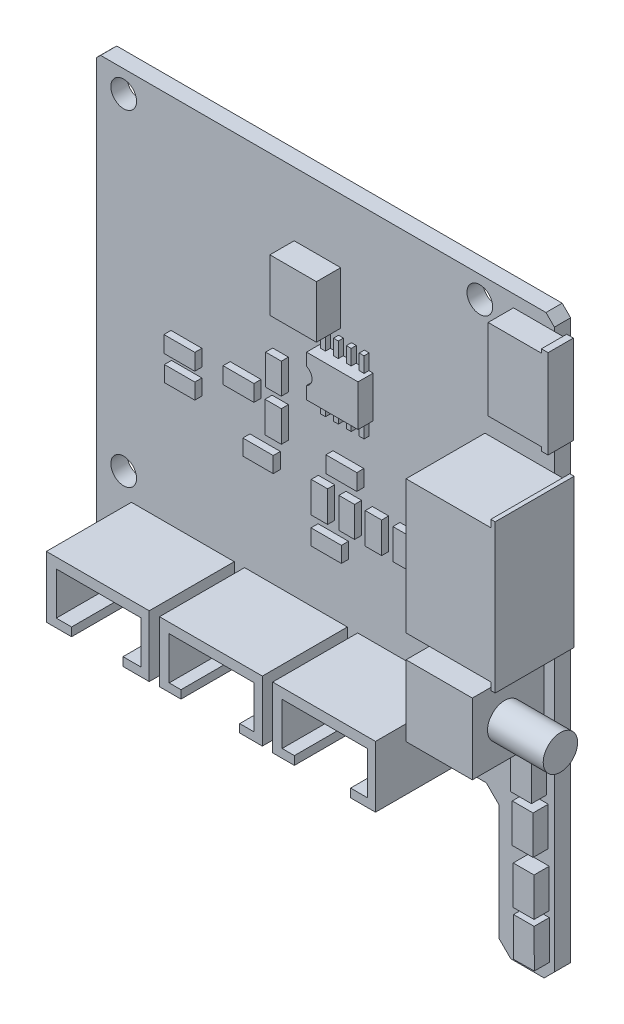
SolidWorks part; units mm, degrees
ref_plane "前视基准面" through (0, 0, 0) normal (0, 0, 1) x (1, 0, 0)
ref_plane "上视基准面" through (0, 0, 0) normal (0, 1, 0) x (1, 0, 0)
ref_plane "右视基准面" through (0, 0, 0) normal (1, 0, 0) x (0, 0, -1)
sketch "Model" plane through (0, 0, 0) normal (0, 0, 1) x (1, 0, 0)
  line L0 (45.593, 67.31) -> (54.991, 57.912)
  line L1 (54.991, 57.912) -> (54.991, 51.054)
  line L2 (54.991, 51.054) -> (56.896, 49.149)
  line L3 (56.896, 49.149) -> (58.801, 49.149)
  line L4 (46.863, 67.31) -> (58.928, 55.245)
  line L5 (58.928, 55.245) -> (58.928, 50.292)
  line L6 (58.928, 50.292) -> (62.992, 46.228)
  line L7 (62.992, 46.228) -> (62.992, 41.529)
  line L8 (62.992, 41.529) -> (65.151, 39.37)
  line L9 (48.133, 67.31) -> (61.214, 54.229)
  line L10 (61.214, 54.229) -> (62.611, 54.229)
  line L11 (62.611, 54.229) -> (65.659, 51.181)
  line L12 (65.659, 51.181) -> (65.659, 47.371)
  line L13 (65.659, 47.371) -> (65.405, 47.117)
  line L14 (65.405, 47.117) -> (65.024, 47.117)
  line L15 (65.024, 47.117) -> (64.897, 46.99)
  line L16 (64.897, 46.99) -> (65.786, 46.101)
  line L17 (65.786, 46.101) -> (65.786, 41.656)
  line L18 (65.151, 37.211) -> (65.786, 37.846)
  line L19 (65.786, 37.846) -> (65.786, 41.656)
  line L20 (65.786, 41.656) -> (65.024, 42.418)
  line L21 (66.167, 32.766) -> (65.151, 32.766)
  line L22 (49.022, 76.327) -> (51.689, 76.327)
  line L23 (44.45, 76.2) -> (46.355, 76.2)
  line L24 (39.624, 64.262) -> (45.339, 64.262)
  line L25 (41.91, 65.659) -> (43.561, 65.659)
  line L26 (43.561, 65.659) -> (44.323, 66.421)
  line L27 (44.323, 66.421) -> (44.323, 66.929)
  line L28 (66.675, 86.5429) -> (66.675, 86.36)
  line L29 (66.675, 86.36) -> (66.675, 86.5427)
  line L30 (66.675, 86.5427) -> (66.675, 31.496)
  line L31 (21.463, 87.0077) -> (21.844, 87.376)
  line L32 (21.844, 87.376) -> (65.8419, 87.376)
  line L33 (65.8419, 87.376) -> (66.675, 86.5429)
  line L34 (21.463, 86.995) -> (21.463, 87.0077)
  line L35 (21.463, 87.0077) -> (21.463, 45.847)
  line L36 (21.463, 45.847) -> (23.114, 44.196)
  line L37 (23.114, 44.196) -> (59.944, 44.196)
  line L38 (59.944, 44.196) -> (61.214, 42.926)
  line L39 (61.214, 42.926) -> (61.214, 31.496)
  line L40 (61.214, 31.496) -> (62.357, 30.353)
  line L41 (62.357, 30.353) -> (65.659, 30.353)
  line L42 (65.659, 30.353) -> (66.675, 31.369)
  line L43 (66.675, 31.369) -> (66.675, 31.496)
  line L44 (57.769, 56.007) -> (58.928, 56.007)
  line L45 (58.928, 56.007) -> (63.119, 51.816)
  line L46 (29.353, 66.548) -> (29.353, 64.008)
  line L47 (28.448, 58.166) -> (29.353, 59.071)
  line L48 (29.353, 59.071) -> (29.353, 64.008)
  line L49 (31.353, 64.008) -> (33.766, 61.595)
  line L50 (33.766, 61.595) -> (37.1, 61.595)
  line L51 (55.769, 56.007) -> (53.848, 57.928)
  line L52 (53.848, 57.928) -> (53.848, 61.468)
  line L53 (53.848, 61.468) -> (54.864, 62.484)
  line L54 (54.864, 62.484) -> (56.007, 62.484)
  line L55 (56.007, 62.484) -> (56.769, 63.246)
  line L56 (56.769, 63.246) -> (56.769, 71.628)
  line L57 (56.769, 71.628) -> (55.753, 72.644)
  line L58 (55.753, 72.644) -> (54.102, 72.644)
  line L59 (54.102, 72.644) -> (53.34, 73.406)
  line L60 (53.34, 73.406) -> (53.34, 74.676)
  line L61 (53.34, 74.676) -> (51.689, 76.327)
  line L62 (64.897, 47.0814) -> (66.04, 45.9384)
  line L63 (66.04, 45.9384) -> (66.04, 42.672)
  line L64 (66.04, 42.672) -> (65.753, 42.3824)
  line L65 (65.753, 42.3824) -> (65.024, 42.3824)
  line L66 (58.801, 49.149) -> (58.8353, 49.1833)
  line L67 (58.8353, 49.1833) -> (64.897, 49.1833)
  line L68 (65.151, 39.4043) -> (63.754, 38.0073)
  line L69 (63.754, 38.0073) -> (63.754, 35.306)
  line L70 (63.754, 35.306) -> (64.2278, 34.8323)
  line L71 (64.2278, 34.8323) -> (65.151, 34.8323)
  line L72 (64.897, 49.1833) -> (63.5, 47.7863)
  line L73 (63.5, 47.7863) -> (63.5, 44.958)
  line L74 (63.5, 44.958) -> (63.9738, 44.4843)
  line L75 (63.9738, 44.4843) -> (65.024, 44.4843)
  line L76 (65.151, 32.7317) -> (66.421, 34.0017)
  line L77 (66.421, 34.0017) -> (66.421, 36.703)
  line L78 (66.421, 36.703) -> (65.8202, 37.3037)
  line L79 (65.8202, 37.3037) -> (65.151, 37.3037)
  line L80 (48.133, 68.7197) -> (48.133, 67.31)
  line L81 (46.863, 68.7197) -> (46.863, 67.31)
  line L82 (45.593, 68.7197) -> (45.593, 67.31)
  line L83 (41.529, 58.293) -> (41.529, 61.325)
  line L84 (41.529, 61.325) -> (43.053, 62.849)
  line L85 (39.1, 61.595) -> (40.132, 60.563)
  line L86 (40.132, 60.563) -> (40.132, 57.531)
  line L87 (40.132, 57.531) -> (40.767, 56.896)
  line L88 (40.767, 56.896) -> (43.45, 56.896)
  line L89 (43.45, 56.896) -> (43.831, 57.277)
  line L90 (48.133, 74.5363) -> (48.133, 75.819)
  line L91 (48.133, 75.819) -> (48.641, 76.327)
  line L92 (48.641, 76.327) -> (49.022, 76.327)
  line L93 (46.355, 76.2) -> (46.863, 75.692)
  line L94 (46.863, 75.692) -> (46.863, 74.5363)
  line L95 (39.1008, 61.595) -> (38.227, 62.4688)
  line L96 (38.227, 62.4688) -> (38.227, 71.12)
  line L97 (38.227, 71.12) -> (43.307, 76.2)
  line L98 (43.307, 76.2) -> (44.45, 76.2)
  line L99 (44.323, 66.929) -> (44.704, 66.548)
  line L100 (44.704, 66.548) -> (49.276, 66.548)
  line L101 (49.276, 66.548) -> (50.165, 67.437)
  line L102 (50.165, 67.437) -> (50.165, 75.819)
  line L103 (50.165, 75.819) -> (55.2145, 80.8685)
  line L104 (55.2145, 80.8685) -> (62.8096, 80.8685)
  line L105 (37.195, 66.802) -> (37.1, 66.707)
  line L106 (37.1, 66.707) -> (37.1, 61.595)
  line L107 (41.0571, 78.486) -> (37.195, 74.6239)
  line L108 (37.195, 74.6239) -> (37.195, 66.802)
  line L109 (36.068, 58.293) -> (38.989, 58.293)
  line L110 (31.2414, 52.205) -> (34.6624, 55.626)
  line L111 (34.6624, 55.626) -> (40.767, 55.626)
  line L112 (40.767, 55.626) -> (42.4174, 53.9756)
  line L113 (42.4174, 53.9756) -> (42.4174, 52.205)
  line L114 (42.4174, 52.205) -> (45.4574, 55.245)
  line L115 (45.4574, 55.245) -> (52.705, 55.245)
  line L116 (52.705, 55.245) -> (53.5934, 54.3566)
  line L117 (53.5934, 54.3566) -> (53.5934, 52.205)
  line L118 (31.2414, 52.205) -> (31.2414, 59.8164)
  line L119 (31.2414, 59.8164) -> (33.02, 61.595)
  line L120 (33.02, 61.595) -> (37.1, 61.595)
  line L121 (45.593, 74.5363) -> (45.5569, 74.5724)
  line L122 (45.5569, 74.5724) -> (45.5569, 78.486)
  line L123 (44.323, 66.929) -> (44.323, 68.7197)
  line L124 (39.624, 66.278) -> (40.243, 65.659)
  line L125 (40.243, 65.659) -> (41.91, 65.659)
  line L126 (44.196, 61.706) -> (43.053, 62.849)
  line L127 (43.053, 62.849) -> (43.053, 73.025)
  line L128 (43.053, 73.025) -> (44.323, 74.295)
  line L129 (44.323, 74.295) -> (44.323, 74.5363)
  line L130 (52.197, 61.706) -> (54.3258, 63.8348)
  line L131 (54.3258, 63.8348) -> (54.3258, 63.9326)
  line L132 (44.196, 61.706) -> (52.197, 61.706)
  line L133 (39.624, 66.278) -> (39.624, 68.342)
  line L134 (59.119, 50.8561) -> (59.119, 57.8561)
  line L135 (65.6689, 50.8561) -> (65.6689, 57.8561)
  line L136 (59.119, 50.8561) -> (65.6689, 50.8561)
  line L137 (59.119, 57.8561) -> (65.6689, 57.8561)
  line L138 (65.659, 55.88) -> (71.755, 55.88)
  line L139 (65.659, 52.832) -> (71.755, 52.832)
  line L140 (71.755, 52.88) -> (71.755, 55.88)
  line L141 (37.719, 57.023) -> (37.719, 59.5376)
  line L142 (37.719, 59.5376) -> (42.799, 59.5376)
  line L143 (42.799, 59.5376) -> (42.799, 57.023)
  line L144 (42.799, 57.023) -> (37.719, 57.023)
  line L145 (32.258, 57.023) -> (32.258, 59.5376)
  line L146 (32.258, 59.5376) -> (37.338, 59.5376)
  line L147 (37.338, 59.5376) -> (37.338, 57.023)
  line L148 (37.338, 57.023) -> (32.258, 57.023)
  line L149 (43.6781, 73.678) -> (48.7782, 73.678)
  line L150 (48.7779, 73.678) -> (48.7779, 69.578)
  line L151 (48.7779, 69.578) -> (43.6778, 69.578)
  line L152 (43.6781, 72.4281) -> (43.6781, 73.678)
  line L153 (43.6781, 70.8279) -> (43.6781, 69.578)
  line L154 (35.0503, 44.6046) -> (24.8916, 44.6046)
  line L155 (35.0503, 50.665) -> (32.1226, 50.665)
  line L156 (30.3603, 50.665) -> (29.5827, 50.665)
  line L157 (27.8204, 50.665) -> (24.8916, 50.665)
  line L158 (35.0503, 44.6046) -> (35.0503, 44.6731)
  line L159 (35.0503, 49.0369) -> (35.0503, 50.665)
  line L160 (24.8916, 44.6046) -> (24.8916, 44.6731)
  line L161 (24.8916, 49.0369) -> (24.8916, 50.665)
  line L162 (46.2263, 44.6046) -> (36.0676, 44.6046)
  line L163 (46.2263, 50.665) -> (43.2986, 50.665)
  line L164 (41.5363, 50.665) -> (40.7587, 50.665)
  line L165 (38.9964, 50.665) -> (36.0676, 50.665)
  line L166 (46.2263, 44.6046) -> (46.2263, 44.6731)
  line L167 (46.2263, 49.0369) -> (46.2263, 50.665)
  line L168 (36.0676, 44.6046) -> (36.0676, 44.6731)
  line L169 (36.0676, 49.0369) -> (36.0676, 50.665)
  line L170 (57.4023, 44.6046) -> (47.2436, 44.6046)
  line L171 (57.4023, 50.665) -> (54.4746, 50.665)
  line L172 (52.7123, 50.665) -> (51.9347, 50.665)
  line L173 (50.1724, 50.665) -> (47.2436, 50.665)
  line L174 (57.4023, 44.6046) -> (57.4023, 44.6731)
  line L175 (57.4023, 49.0369) -> (57.4023, 50.665)
  line L176 (47.2436, 44.6046) -> (47.2436, 44.6731)
  line L177 (47.2436, 49.0369) -> (47.2436, 50.665)
  line L178 (64.524, 43.634) -> (65.5243, 43.634)
  line L179 (66.0667, 43.0898) -> (66.0667, 41.6166)
  line L180 (66.0667, 41.6166) -> (65.6603, 41.2102)
  line L181 (65.6603, 41.2102) -> (64.3903, 41.2102)
  line L182 (64.3903, 41.2102) -> (64.0093, 41.5912)
  line L183 (64.0093, 41.5912) -> (64.0093, 43.1152)
  line L184 (66.0413, 43.8772) -> (66.0413, 45.4266)
  line L185 (66.0413, 45.4266) -> (64.0093, 45.4266)
  line L186 (64.0093, 45.4266) -> (64.0093, 43.8772)
  line L187 (65.024, 43.5341) -> (65.024, 43.2651)
  line L188 (65.397, 47.933) -> (64.3967, 47.933)
  line L189 (63.8543, 48.4772) -> (63.8543, 49.9504)
  line L190 (63.8543, 49.9504) -> (64.2607, 50.3568)
  line L191 (64.2607, 50.3568) -> (65.5307, 50.3568)
  line L192 (65.5307, 50.3568) -> (65.9117, 49.9758)
  line L193 (65.9117, 49.9758) -> (65.9117, 48.4518)
  line L194 (63.8797, 47.6898) -> (63.8797, 46.1404)
  line L195 (63.8797, 46.1404) -> (65.9117, 46.1404)
  line L196 (65.9117, 46.1404) -> (65.9117, 47.6898)
  line L197 (64.897, 48.0329) -> (64.897, 48.3019)
  line L198 (65.651, 38.154) -> (64.6507, 38.154)
  line L199 (64.1083, 38.6982) -> (64.1083, 40.1714)
  line L200 (64.1083, 40.1714) -> (64.5147, 40.5778)
  line L201 (64.5147, 40.5778) -> (65.7847, 40.5778)
  line L202 (65.7847, 40.5778) -> (66.1657, 40.1968)
  line L203 (66.1657, 40.1968) -> (66.1657, 38.6728)
  line L204 (64.1337, 37.9108) -> (64.1337, 36.3614)
  line L205 (64.1337, 36.3614) -> (66.1657, 36.3614)
  line L206 (66.1657, 36.3614) -> (66.1657, 37.9108)
  line L207 (65.151, 38.2539) -> (65.151, 38.5229)
  line L208 (64.651, 33.982) -> (65.6513, 33.982)
  line L209 (66.1937, 33.4378) -> (66.1937, 31.9646)
  line L210 (66.1937, 31.9646) -> (65.7873, 31.5582)
  line L211 (65.7873, 31.5582) -> (64.5173, 31.5582)
  line L212 (64.5173, 31.5582) -> (64.1363, 31.9392)
  line L213 (64.1363, 31.9392) -> (64.1363, 33.4632)
  line L214 (66.1683, 34.2252) -> (66.1683, 35.7746)
  line L215 (66.1683, 35.7746) -> (64.1363, 35.7746)
  line L216 (64.1363, 35.7746) -> (64.1363, 34.2252)
  line L217 (65.151, 33.8821) -> (65.151, 33.6131)
  line L218 (68.1955, 74.0424) -> (59.829, 74.0419)
  line L219 (59.819, 60.8519) -> (68.2485, 60.8553)
  line L220 (54.6259, 71.7639) -> (54.6251, 73.3414)
  line L221 (54.6259, 69.2645) -> (54.6259, 70.1016)
  line L222 (54.6259, 67.263) -> (54.6259, 67.6022)
  line L223 (54.6259, 64.7636) -> (54.6259, 65.6007)
  line L224 (60.8498, 71.7902) -> (54.6277, 71.7902)
  line L225 (60.8398, 63.0736) -> (54.6274, 63.0736)
  line L226 (65.3631, 69.9817) -> (65.3631, 72.0117)
  line L227 (64.153, 69.8418) -> (64.153, 72.1019)
  line L228 (65.264, 63.1006) -> (65.264, 65.1306)
  line L229 (64.054, 62.9607) -> (64.054, 65.2208)
  line L230 (61.7888, 65.9089) -> (67.5292, 65.5533)
  line L231 (67.5292, 65.5533) -> (67.5292, 62.6577)
  line L232 (67.5292, 62.6577) -> (61.7888, 62.1751)
  line L233 (61.7888, 62.1751) -> (61.7888, 62.6831)
  line L234 (61.7888, 62.6831) -> (66.9239, 63.1883)
  line L235 (66.9239, 63.1883) -> (66.9239, 64.9386)
  line L236 (66.9239, 64.9386) -> (61.7888, 65.5279)
  line L237 (61.7888, 65.5279) -> (61.7888, 65.9089)
  line L238 (61.8576, 72.7376) -> (67.5942, 72.3897)
  line L239 (67.5942, 72.3897) -> (67.5894, 69.5045)
  line L240 (67.5894, 69.5045) -> (61.8543, 69.0094)
  line L241 (61.8543, 69.0094) -> (61.8581, 69.5182)
  line L242 (61.8581, 69.5182) -> (66.3984, 70.0285)
  line L243 (66.3984, 70.0285) -> (67.0766, 70.1037)
  line L244 (67.0766, 70.1037) -> (67.0659, 71.8535)
  line L245 (67.0659, 71.8535) -> (62.2877, 72.3274)
  line L246 (62.2877, 72.3274) -> (61.8576, 72.3574)
  line L247 (61.8576, 72.3574) -> (61.8576, 72.7376)
  line L248 (58.6582, 61.5324) -> (58.6499, 62.3653)
  line L249 (58.6499, 62.3653) -> (60.851, 62.3653)
  line L250 (60.851, 62.3653) -> (60.851, 72.5052)
  line L251 (60.851, 72.5052) -> (58.6501, 72.5052)
  line L252 (58.6501, 72.5052) -> (58.6582, 73.3314)
  line L253 (54.6259, 63.1013) -> (54.6251, 61.5324)
  line L254 (68.4457, 74.7625) -> (68.6255, 74.7625)
  line L255 (68.4457, 60.1125) -> (68.6255, 60.1125)
  line L256 (68.1056, 61.3724) -> (68.2865, 61.1928)
  line L257 (68.2865, 61.1928) -> (68.6266, 60.8527)
  line L258 (68.1056, 73.5225) -> (68.2865, 73.7028)
  line L259 (68.2865, 73.7028) -> (68.6164, 74.0327)
  line L260 (68.6266, 60.1227) -> (68.6266, 60.8527)
  line L261 (68.6266, 60.8527) -> (68.3764, 60.8527)
  line L262 (68.1056, 61.4425) -> (68.1056, 61.1925)
  line L263 (68.1056, 61.1925) -> (68.4457, 60.8524)
  line L264 (68.1056, 73.4524) -> (68.1056, 73.7025)
  line L265 (68.1056, 73.7025) -> (68.4356, 74.0325)
  line L266 (68.4457, 74.7523) -> (68.4457, 74.0424)
  line L267 (68.4457, 74.0424) -> (68.1955, 74.0424)
  line L268 (68.4457, 60.1224) -> (68.4457, 60.8524)
  line L269 (68.4457, 60.8524) -> (68.1955, 60.8524)
  line L270 (68.1056, 61.4425) -> (68.1056, 73.4424)
  line L271 (68.6266, 74.7526) -> (68.6266, 74.0427)
  line L272 (68.6266, 74.0427) -> (68.3764, 74.0427)
  line L273 (45.557, 80.01) -> (45.5676, 81.0768)
  line L274 (45.5676, 81.0768) -> (40.9956, 81.0768)
  line L275 (40.9956, 81.0768) -> (40.985, 80.01)
  line L276 (45.557, 76.962) -> (45.5676, 75.8952)
  line L277 (45.5676, 75.8952) -> (40.9702, 75.8952)
  line L278 (40.9702, 75.8952) -> (40.985, 76.962)
  line L279 (37.945, 67.602) -> (37.945, 66.002)
  line L280 (34.445, 67.602) -> (34.445, 66.002)
  line L281 (36.695, 65.762) -> (37.745, 65.762)
  line L282 (36.695, 67.842) -> (37.745, 67.842)
  line L283 (35.695, 65.762) -> (34.645, 65.762)
  line L284 (35.695, 67.842) -> (34.645, 67.842)
  line L285 (34.445, 67.6219) -> (34.445, 67.602)
  line L286 (34.445, 67.642) -> (34.445, 67.602)
  line L287 (34.445, 65.962) -> (34.445, 66.002)
  line L288 (37.945, 67.642) -> (37.945, 67.602)
  line L289 (37.945, 65.962) -> (37.945, 66.002)
  line L290 (43.081, 56.477) -> (43.081, 58.077)
  line L291 (46.581, 56.477) -> (46.581, 58.077)
  line L292 (44.331, 58.317) -> (43.281, 58.317)
  line L293 (44.331, 56.237) -> (43.281, 56.237)
  line L294 (45.331, 58.317) -> (46.381, 58.317)
  line L295 (45.331, 56.237) -> (46.381, 56.237)
  line L296 (46.581, 56.4571) -> (46.581, 56.477)
  line L297 (46.581, 56.437) -> (46.581, 56.477)
  line L298 (46.581, 58.117) -> (46.581, 58.077)
  line L299 (43.081, 56.437) -> (43.081, 56.477)
  line L300 (43.081, 58.117) -> (43.081, 58.077)
  line L301 (44.996, 58.956) -> (43.396, 58.956)
  line L302 (44.996, 62.456) -> (43.396, 62.456)
  line L303 (43.156, 60.206) -> (43.156, 59.156)
  line L304 (45.236, 60.206) -> (45.236, 59.156)
  line L305 (43.156, 61.206) -> (43.156, 62.256)
  line L306 (45.236, 61.206) -> (45.236, 62.256)
  line L307 (45.0159, 62.456) -> (44.996, 62.456)
  line L308 (45.036, 62.456) -> (44.996, 62.456)
  line L309 (43.356, 62.456) -> (43.396, 62.456)
  line L310 (45.036, 58.956) -> (44.996, 58.956)
  line L311 (43.356, 58.956) -> (43.396, 58.956)
  line L312 (47.663, 58.956) -> (46.063, 58.956)
  line L313 (47.663, 62.456) -> (46.063, 62.456)
  line L314 (45.823, 60.206) -> (45.823, 59.156)
  line L315 (47.903, 60.206) -> (47.903, 59.156)
  line L316 (45.823, 61.206) -> (45.823, 62.256)
  line L317 (47.903, 61.206) -> (47.903, 62.256)
  line L318 (47.6829, 62.456) -> (47.663, 62.456)
  line L319 (47.703, 62.456) -> (47.663, 62.456)
  line L320 (46.023, 62.456) -> (46.063, 62.456)
  line L321 (47.703, 58.956) -> (47.663, 58.956)
  line L322 (46.023, 58.956) -> (46.063, 58.956)
  line L323 (50.33, 58.956) -> (48.73, 58.956)
  line L324 (50.33, 62.456) -> (48.73, 62.456)
  line L325 (48.49, 60.206) -> (48.49, 59.156)
  line L326 (50.57, 60.206) -> (50.57, 59.156)
  line L327 (48.49, 61.206) -> (48.49, 62.256)
  line L328 (50.57, 61.206) -> (50.57, 62.256)
  line L329 (50.3499, 62.456) -> (50.33, 62.456)
  line L330 (50.37, 62.456) -> (50.33, 62.456)
  line L331 (48.69, 62.456) -> (48.73, 62.456)
  line L332 (50.37, 58.956) -> (50.33, 58.956)
  line L333 (48.69, 58.956) -> (48.73, 58.956)
  line L334 (52.997, 58.956) -> (51.397, 58.956)
  line L335 (52.997, 62.456) -> (51.397, 62.456)
  line L336 (51.157, 60.206) -> (51.157, 59.156)
  line L337 (53.237, 60.206) -> (53.237, 59.156)
  line L338 (51.157, 61.206) -> (51.157, 62.256)
  line L339 (53.237, 61.206) -> (53.237, 62.256)
  line L340 (53.0169, 62.456) -> (52.997, 62.456)
  line L341 (53.037, 62.456) -> (52.997, 62.456)
  line L342 (51.357, 62.456) -> (51.397, 62.456)
  line L343 (53.037, 58.956) -> (52.997, 58.956)
  line L344 (51.357, 58.956) -> (51.397, 58.956)
  line L345 (38.824, 71.092) -> (40.424, 71.092)
  line L346 (38.824, 67.592) -> (40.424, 67.592)
  line L347 (40.664, 69.842) -> (40.664, 70.892)
  line L348 (38.584, 69.842) -> (38.584, 70.892)
  line L349 (40.664, 68.842) -> (40.664, 67.792)
  line L350 (38.584, 68.842) -> (38.584, 67.792)
  line L351 (38.8041, 67.592) -> (38.824, 67.592)
  line L352 (38.784, 67.592) -> (38.824, 67.592)
  line L353 (40.464, 67.592) -> (40.424, 67.592)
  line L354 (38.784, 71.092) -> (38.824, 71.092)
  line L355 (40.464, 71.092) -> (40.424, 71.092)
  line L356 (48.105, 65.062) -> (48.105, 63.462)
  line L357 (44.605, 65.062) -> (44.605, 63.462)
  line L358 (46.855, 63.222) -> (47.905, 63.222)
  line L359 (46.855, 65.302) -> (47.905, 65.302)
  line L360 (45.855, 63.222) -> (44.805, 63.222)
  line L361 (45.855, 65.302) -> (44.805, 65.302)
  line L362 (44.605, 65.0819) -> (44.605, 65.062)
  line L363 (44.605, 65.102) -> (44.605, 65.062)
  line L364 (44.605, 63.422) -> (44.605, 63.462)
  line L365 (48.105, 65.102) -> (48.105, 65.062)
  line L366 (48.105, 63.422) -> (48.105, 63.462)
  line L367 (55.019, 55.207) -> (55.019, 56.807)
  line L368 (58.519, 55.207) -> (58.519, 56.807)
  line L369 (56.269, 57.047) -> (55.219, 57.047)
  line L370 (56.269, 54.967) -> (55.219, 54.967)
  line L371 (57.269, 57.047) -> (58.319, 57.047)
  line L372 (57.269, 54.967) -> (58.319, 54.967)
  line L373 (58.519, 55.1871) -> (58.519, 55.207)
  line L374 (58.519, 55.167) -> (58.519, 55.207)
  line L375 (58.519, 56.847) -> (58.519, 56.807)
  line L376 (55.019, 55.167) -> (55.019, 55.207)
  line L377 (55.019, 56.847) -> (55.019, 56.807)
  line L378 (36.35, 60.795) -> (36.35, 62.395)
  line L379 (39.85, 60.795) -> (39.85, 62.395)
  line L380 (37.6, 62.635) -> (36.55, 62.635)
  line L381 (37.6, 60.555) -> (36.55, 60.555)
  line L382 (38.6, 62.635) -> (39.65, 62.635)
  line L383 (38.6, 60.555) -> (39.65, 60.555)
  line L384 (39.85, 60.7751) -> (39.85, 60.795)
  line L385 (39.85, 60.755) -> (39.85, 60.795)
  line L386 (39.85, 62.435) -> (39.85, 62.395)
  line L387 (36.35, 60.755) -> (36.35, 60.795)
  line L388 (36.35, 62.435) -> (36.35, 62.395)
  line L389 (40.424, 63.528) -> (38.824, 63.528)
  line L390 (40.424, 67.028) -> (38.824, 67.028)
  line L391 (38.584, 64.778) -> (38.584, 63.728)
  line L392 (40.664, 64.778) -> (40.664, 63.728)
  line L393 (38.584, 65.778) -> (38.584, 66.828)
  line L394 (40.664, 65.778) -> (40.664, 66.828)
  line L395 (40.4439, 67.028) -> (40.424, 67.028)
  line L396 (40.464, 67.028) -> (40.424, 67.028)
  line L397 (38.784, 67.028) -> (38.824, 67.028)
  line L398 (40.464, 63.528) -> (40.424, 63.528)
  line L399 (38.784, 63.528) -> (38.824, 63.528)
  line L400 (68.1309, 86.1593) -> (68.55, 86.5454)
  line L401 (68.55, 86.5454) -> (68.55, 86.2533)
  line L402 (68.55, 86.2533) -> (67.8896, 85.6437)
  line L403 (67.8896, 85.6437) -> (67.8896, 78.629)
  line L404 (67.8896, 78.629) -> (68.6008, 77.9653)
  line L405 (68.6008, 77.9653) -> (68.6008, 77.8002)
  line L406 (68.6008, 77.8002) -> (68.55, 77.8002)
  line L407 (68.55, 77.8002) -> (68.1309, 78.1583)
  line L408 (62.6293, 78.1685) -> (62.6293, 80.4113)
  line L409 (62.6293, 83.9267) -> (62.6293, 86.1695)
  line L410 (66.6603, 86.1695) -> (68.2529, 86.1695)
  line L411 (66.6603, 78.1685) -> (68.1309, 78.1685)
  line L412 (66.6603, 78.1685) -> (66.5955, 78.1685)
  line L413 (64.8332, 78.1685) -> (64.0415, 78.1685)
  line L414 (62.6792, 78.1685) -> (62.6293, 78.1685)
  line L415 (66.6603, 86.1695) -> (66.5955, 86.1695)
  line L416 (64.8332, 86.1695) -> (64.0415, 86.1695)
  line L417 (62.6792, 86.1695) -> (62.6293, 86.1695)
  line L418 (24.638, 56.896) -> (24.638, 59.4106)
  line L419 (24.638, 59.4106) -> (29.718, 59.4106)
  line L420 (29.718, 59.4106) -> (29.718, 56.896)
  line L421 (29.718, 56.896) -> (24.638, 56.896)
  line L422 (32.103, 64.808) -> (32.103, 63.208)
  line L423 (28.603, 64.808) -> (28.603, 63.208)
  line L424 (30.853, 62.968) -> (31.903, 62.968)
  line L425 (30.853, 65.048) -> (31.903, 65.048)
  line L426 (29.853, 62.968) -> (28.803, 62.968)
  line L427 (29.853, 65.048) -> (28.803, 65.048)
  line L428 (28.603, 64.8279) -> (28.603, 64.808)
  line L429 (28.603, 64.848) -> (28.603, 64.808)
  line L430 (28.603, 63.168) -> (28.603, 63.208)
  line L431 (32.103, 64.848) -> (32.103, 64.808)
  line L432 (32.103, 63.168) -> (32.103, 63.208)
  line L433 (28.603, 65.748) -> (28.603, 67.348)
  line L434 (32.103, 65.748) -> (32.103, 67.348)
  line L435 (29.853, 67.588) -> (28.803, 67.588)
  line L436 (29.853, 65.508) -> (28.803, 65.508)
  line L437 (30.853, 67.588) -> (31.903, 67.588)
  line L438 (30.853, 65.508) -> (31.903, 65.508)
  line L439 (32.103, 65.7281) -> (32.103, 65.748)
  line L440 (32.103, 65.708) -> (32.103, 65.748)
  line L441 (32.103, 67.388) -> (32.103, 67.348)
  line L442 (28.603, 65.708) -> (28.603, 65.748)
  line L443 (28.603, 67.388) -> (28.603, 67.348)
  line L444 (40.7416, 57.5056) -> (40.7416, 59.0804)
  line L445 (40.7416, 59.0804) -> (42.3164, 59.0804)
  line L446 (42.3164, 59.0804) -> (42.3164, 57.5056)
  line L447 (42.3164, 57.5056) -> (40.7416, 57.5056)
  line L448 (35.2806, 57.5056) -> (35.2806, 59.0804)
  line L449 (35.2806, 59.0804) -> (36.8554, 59.0804)
  line L450 (36.8554, 59.0804) -> (36.8554, 57.5056)
  line L451 (36.8554, 57.5056) -> (35.2806, 57.5056)
  line L452 (44.083, 68.0697) -> (44.083, 69.3697)
  line L453 (44.083, 69.3697) -> (44.563, 69.3697)
  line L454 (44.563, 69.3697) -> (44.563, 68.0697)
  line L455 (44.563, 68.0697) -> (44.083, 68.0697)
  line L456 (45.353, 68.0697) -> (45.353, 69.3697)
  line L457 (45.353, 69.3697) -> (45.833, 69.3697)
  line L458 (45.833, 69.3697) -> (45.833, 68.0697)
  line L459 (45.833, 68.0697) -> (45.353, 68.0697)
  line L460 (46.623, 68.0697) -> (46.623, 69.3697)
  line L461 (46.623, 69.3697) -> (47.103, 69.3697)
  line L462 (47.103, 69.3697) -> (47.103, 68.0697)
  line L463 (47.103, 68.0697) -> (46.623, 68.0697)
  line L464 (47.893, 68.0697) -> (47.893, 69.3697)
  line L465 (47.893, 69.3697) -> (48.373, 69.3697)
  line L466 (48.373, 69.3697) -> (48.373, 68.0697)
  line L467 (48.373, 68.0697) -> (47.893, 68.0697)
  line L468 (47.893, 73.8863) -> (47.893, 75.1863)
  line L469 (47.893, 75.1863) -> (48.373, 75.1863)
  line L470 (48.373, 75.1863) -> (48.373, 73.8863)
  line L471 (48.373, 73.8863) -> (47.893, 73.8863)
  line L472 (46.623, 73.8863) -> (46.623, 75.1863)
  line L473 (46.623, 75.1863) -> (47.103, 75.1863)
  line L474 (47.103, 75.1863) -> (47.103, 73.8863)
  line L475 (47.103, 73.8863) -> (46.623, 73.8863)
  line L476 (45.353, 73.8863) -> (45.353, 75.1863)
  line L477 (45.353, 75.1863) -> (45.833, 75.1863)
  line L478 (45.833, 75.1863) -> (45.833, 73.8863)
  line L479 (45.833, 73.8863) -> (45.353, 73.8863)
  line L480 (44.083, 73.8863) -> (44.083, 75.1863)
  line L481 (44.083, 75.1863) -> (44.563, 75.1863)
  line L482 (44.563, 75.1863) -> (44.563, 73.8863)
  line L483 (44.563, 73.8863) -> (44.083, 73.8863)
  line L484 (47.9781, 70.3781) -> (44.4779, 70.3781)
  line L485 (44.4779, 70.3781) -> (44.4779, 72.8779)
  line L486 (44.4779, 72.8779) -> (47.9781, 72.8779)
  line L487 (47.9781, 72.8779) -> (47.9781, 70.3781)
  line L488 (31.8915, 49.955) -> (30.5915, 49.955)
  line L489 (30.5915, 49.955) -> (30.5915, 54.455)
  line L490 (30.5915, 54.455) -> (31.8915, 54.455)
  line L491 (31.8915, 54.455) -> (31.8915, 49.955)
  line L492 (29.3515, 49.955) -> (28.0515, 49.955)
  line L493 (28.0515, 49.955) -> (28.0515, 54.455)
  line L494 (28.0515, 54.455) -> (29.3515, 54.455)
  line L495 (29.3515, 54.455) -> (29.3515, 49.955)
  line L496 (35.3424, 44.9043) -> (33.5416, 44.9043)
  line L497 (33.5416, 44.9043) -> (33.5416, 48.8057)
  line L498 (33.5416, 48.8057) -> (35.3424, 48.8057)
  line L499 (35.3424, 48.8057) -> (35.3424, 44.9043)
  line L500 (26.4025, 44.9043) -> (24.6016, 44.9043)
  line L501 (24.6016, 44.9043) -> (24.6016, 48.8057)
  line L502 (24.6016, 48.8057) -> (26.4025, 48.8057)
  line L503 (26.4025, 48.8057) -> (26.4025, 44.9043)
  line L504 (43.0675, 49.955) -> (41.7675, 49.955)
  line L505 (41.7675, 49.955) -> (41.7675, 54.455)
  line L506 (41.7675, 54.455) -> (43.0675, 54.455)
  line L507 (43.0675, 54.455) -> (43.0675, 49.955)
  line L508 (40.5275, 49.955) -> (39.2275, 49.955)
  line L509 (39.2275, 49.955) -> (39.2275, 54.455)
  line L510 (39.2275, 54.455) -> (40.5275, 54.455)
  line L511 (40.5275, 54.455) -> (40.5275, 49.955)
  line L512 (46.5184, 44.9043) -> (44.7176, 44.9043)
  line L513 (44.7176, 44.9043) -> (44.7176, 48.8057)
  line L514 (44.7176, 48.8057) -> (46.5184, 48.8057)
  line L515 (46.5184, 48.8057) -> (46.5184, 44.9043)
  line L516 (37.5785, 44.9043) -> (35.7776, 44.9043)
  line L517 (35.7776, 44.9043) -> (35.7776, 48.8057)
  line L518 (35.7776, 48.8057) -> (37.5785, 48.8057)
  line L519 (37.5785, 48.8057) -> (37.5785, 44.9043)
  line L520 (54.2435, 49.955) -> (52.9435, 49.955)
  line L521 (52.9435, 49.955) -> (52.9435, 54.455)
  line L522 (52.9435, 54.455) -> (54.2435, 54.455)
  line L523 (54.2435, 54.455) -> (54.2435, 49.955)
  line L524 (51.7035, 49.955) -> (50.4035, 49.955)
  line L525 (50.4035, 49.955) -> (50.4035, 54.455)
  line L526 (50.4035, 54.455) -> (51.7035, 54.455)
  line L527 (51.7035, 54.455) -> (51.7035, 49.955)
  line L528 (57.6944, 44.9043) -> (55.8936, 44.9043)
  line L529 (55.8936, 44.9043) -> (55.8936, 48.8057)
  line L530 (55.8936, 48.8057) -> (57.6944, 48.8057)
  line L531 (57.6944, 48.8057) -> (57.6944, 44.9043)
  line L532 (48.7545, 44.9043) -> (46.9536, 44.9043)
  line L533 (46.9536, 44.9043) -> (46.9536, 48.8057)
  line L534 (46.9536, 48.8057) -> (48.7545, 48.8057)
  line L535 (48.7545, 48.8057) -> (48.7545, 44.9043)
  line L536 (65.7238, 45.1345) -> (65.7238, 43.834)
  line L537 (65.7238, 43.834) -> (64.3242, 43.834)
  line L538 (64.3242, 43.834) -> (64.3242, 45.1345)
  line L539 (64.3242, 45.1345) -> (65.7238, 45.1345)
  line L540 (65.7238, 43.0339) -> (65.7238, 41.7335)
  line L541 (65.7238, 41.7335) -> (64.3242, 41.7335)
  line L542 (64.3242, 41.7335) -> (64.3242, 43.0339)
  line L543 (64.3242, 43.0339) -> (65.7238, 43.0339)
  line L544 (64.1972, 46.4325) -> (64.1972, 47.7329)
  line L545 (64.1972, 47.7329) -> (65.5968, 47.7329)
  line L546 (65.5968, 47.7329) -> (65.5968, 46.4325)
  line L547 (65.5968, 46.4325) -> (64.1972, 46.4325)
  line L548 (64.1972, 48.533) -> (64.1972, 49.8335)
  line L549 (64.1972, 49.8335) -> (65.5968, 49.8335)
  line L550 (65.5968, 49.8335) -> (65.5968, 48.533)
  line L551 (65.5968, 48.533) -> (64.1972, 48.533)
  line L552 (64.4512, 36.6535) -> (64.4512, 37.9539)
  line L553 (64.4512, 37.9539) -> (65.8508, 37.9539)
  line L554 (65.8508, 37.9539) -> (65.8508, 36.6535)
  line L555 (65.8508, 36.6535) -> (64.4512, 36.6535)
  line L556 (64.4512, 38.754) -> (64.4512, 40.0545)
  line L557 (64.4512, 40.0545) -> (65.8508, 40.0545)
  line L558 (65.8508, 40.0545) -> (65.8508, 38.754)
  line L559 (65.8508, 38.754) -> (64.4512, 38.754)
  line L560 (65.8508, 35.4825) -> (65.8508, 34.182)
  line L561 (65.8508, 34.182) -> (64.4512, 34.182)
  line L562 (64.4512, 34.182) -> (64.4512, 35.4825)
  line L563 (64.4512, 35.4825) -> (65.8508, 35.4825)
  line L564 (65.8508, 33.3819) -> (65.8508, 32.0815)
  line L565 (65.8508, 32.0815) -> (64.4512, 32.0815)
  line L566 (64.4512, 32.0815) -> (64.4512, 33.3819)
  line L567 (64.4512, 33.3819) -> (65.8508, 33.3819)
  line L568 (52.4259, 70.3327) -> (52.4259, 71.5327)
  line L569 (52.4259, 71.5327) -> (56.2259, 71.5327)
  line L570 (56.2259, 71.5327) -> (56.2259, 70.3327)
  line L571 (56.2259, 70.3327) -> (52.4259, 70.3327)
  line L572 (52.4259, 67.8334) -> (52.4259, 69.0334)
  line L573 (52.4259, 69.0334) -> (56.2258, 69.0334)
  line L574 (56.2258, 69.0334) -> (56.2258, 67.8334)
  line L575 (56.2258, 67.8334) -> (52.4259, 67.8334)
  line L576 (52.4259, 65.8318) -> (52.4259, 67.0318)
  line L577 (52.4259, 67.0318) -> (56.2258, 67.0318)
  line L578 (56.2258, 67.0318) -> (56.2258, 65.8318)
  line L579 (56.2258, 65.8318) -> (52.4259, 65.8318)
  line L580 (52.4259, 63.3325) -> (52.4259, 64.5325)
  line L581 (52.4259, 64.5325) -> (56.2258, 64.5325)
  line L582 (56.2258, 64.5325) -> (56.2258, 63.3325)
  line L583 (56.2258, 63.3325) -> (52.4259, 63.3325)
  line L584 (59.5759, 58.7869) -> (54.2759, 58.7869)
  line L585 (54.2759, 58.7869) -> (54.2759, 61.2869)
  line L586 (54.2759, 61.2869) -> (59.5759, 61.2869)
  line L587 (59.5759, 61.2869) -> (59.5759, 58.7869)
  line L588 (59.5759, 73.5869) -> (54.2759, 73.5869)
  line L589 (54.2759, 73.5869) -> (54.2759, 76.0869)
  line L590 (54.2759, 76.0869) -> (59.5759, 76.0869)
  line L591 (59.5759, 76.0869) -> (59.5759, 73.5869)
  line L592 (41.8071, 77.236) -> (40.3071, 77.236)
  line L593 (40.3071, 77.236) -> (40.3071, 79.736)
  line L594 (40.3071, 79.736) -> (41.8071, 79.736)
  line L595 (41.8071, 79.736) -> (41.8071, 77.236)
  line L596 (46.3071, 77.236) -> (44.8071, 77.236)
  line L597 (44.8071, 77.236) -> (44.8071, 79.736)
  line L598 (44.8071, 79.736) -> (46.3071, 79.736)
  line L599 (46.3071, 79.736) -> (46.3071, 77.236)
  line L600 (34.695, 67.577) -> (35.695, 67.577)
  line L601 (35.695, 67.577) -> (35.695, 66.027)
  line L602 (35.695, 66.027) -> (34.695, 66.027)
  line L603 (34.695, 66.027) -> (34.695, 67.577)
  line L604 (36.695, 67.577) -> (37.695, 67.577)
  line L605 (37.695, 67.577) -> (37.695, 66.027)
  line L606 (37.695, 66.027) -> (36.695, 66.027)
  line L607 (36.695, 66.027) -> (36.695, 67.577)
  line L608 (46.331, 56.502) -> (45.331, 56.502)
  line L609 (45.331, 56.502) -> (45.331, 58.052)
  line L610 (45.331, 58.052) -> (46.331, 58.052)
  line L611 (46.331, 58.052) -> (46.331, 56.502)
  line L612 (44.331, 56.502) -> (43.331, 56.502)
  line L613 (43.331, 56.502) -> (43.331, 58.052)
  line L614 (43.331, 58.052) -> (44.331, 58.052)
  line L615 (44.331, 58.052) -> (44.331, 56.502)
  line L616 (44.971, 62.206) -> (44.971, 61.206)
  line L617 (44.971, 61.206) -> (43.421, 61.206)
  line L618 (43.421, 61.206) -> (43.421, 62.206)
  line L619 (43.421, 62.206) -> (44.971, 62.206)
  line L620 (44.971, 60.206) -> (44.971, 59.206)
  line L621 (44.971, 59.206) -> (43.421, 59.206)
  line L622 (43.421, 59.206) -> (43.421, 60.206)
  line L623 (43.421, 60.206) -> (44.971, 60.206)
  line L624 (47.638, 62.206) -> (47.638, 61.206)
  line L625 (47.638, 61.206) -> (46.088, 61.206)
  line L626 (46.088, 61.206) -> (46.088, 62.206)
  line L627 (46.088, 62.206) -> (47.638, 62.206)
  line L628 (47.638, 60.206) -> (47.638, 59.206)
  line L629 (47.638, 59.206) -> (46.088, 59.206)
  line L630 (46.088, 59.206) -> (46.088, 60.206)
  line L631 (46.088, 60.206) -> (47.638, 60.206)
  line L632 (50.305, 62.206) -> (50.305, 61.206)
  line L633 (50.305, 61.206) -> (48.755, 61.206)
  line L634 (48.755, 61.206) -> (48.755, 62.206)
  line L635 (48.755, 62.206) -> (50.305, 62.206)
  line L636 (50.305, 60.206) -> (50.305, 59.206)
  line L637 (50.305, 59.206) -> (48.755, 59.206)
  line L638 (48.755, 59.206) -> (48.755, 60.206)
  line L639 (48.755, 60.206) -> (50.305, 60.206)
  line L640 (52.972, 62.206) -> (52.972, 61.206)
  line L641 (52.972, 61.206) -> (51.422, 61.206)
  line L642 (51.422, 61.206) -> (51.422, 62.206)
  line L643 (51.422, 62.206) -> (52.972, 62.206)
  line L644 (52.972, 60.206) -> (52.972, 59.206)
  line L645 (52.972, 59.206) -> (51.422, 59.206)
  line L646 (51.422, 59.206) -> (51.422, 60.206)
  line L647 (51.422, 60.206) -> (52.972, 60.206)
  line L648 (38.849, 67.842) -> (38.849, 68.842)
  line L649 (38.849, 68.842) -> (40.399, 68.842)
  line L650 (40.399, 68.842) -> (40.399, 67.842)
  line L651 (40.399, 67.842) -> (38.849, 67.842)
  line L652 (38.849, 69.842) -> (38.849, 70.842)
  line L653 (38.849, 70.842) -> (40.399, 70.842)
  line L654 (40.399, 70.842) -> (40.399, 69.842)
  line L655 (40.399, 69.842) -> (38.849, 69.842)
  line L656 (44.855, 65.037) -> (45.855, 65.037)
  line L657 (45.855, 65.037) -> (45.855, 63.487)
  line L658 (45.855, 63.487) -> (44.855, 63.487)
  line L659 (44.855, 63.487) -> (44.855, 65.037)
  line L660 (46.855, 65.037) -> (47.855, 65.037)
  line L661 (47.855, 65.037) -> (47.855, 63.487)
  line L662 (47.855, 63.487) -> (46.855, 63.487)
  line L663 (46.855, 63.487) -> (46.855, 65.037)
  line L664 (58.269, 55.232) -> (57.269, 55.232)
  line L665 (57.269, 55.232) -> (57.269, 56.782)
  line L666 (57.269, 56.782) -> (58.269, 56.782)
  line L667 (58.269, 56.782) -> (58.269, 55.232)
  line L668 (56.269, 55.232) -> (55.269, 55.232)
  line L669 (55.269, 55.232) -> (55.269, 56.782)
  line L670 (55.269, 56.782) -> (56.269, 56.782)
  line L671 (56.269, 56.782) -> (56.269, 55.232)
  line L672 (39.6, 60.82) -> (38.6, 60.82)
  line L673 (38.6, 60.82) -> (38.6, 62.37)
  line L674 (38.6, 62.37) -> (39.6, 62.37)
  line L675 (39.6, 62.37) -> (39.6, 60.82)
  line L676 (37.6, 60.82) -> (36.6, 60.82)
  line L677 (36.6, 60.82) -> (36.6, 62.37)
  line L678 (36.6, 62.37) -> (37.6, 62.37)
  line L679 (37.6, 62.37) -> (37.6, 60.82)
  line L680 (40.399, 66.778) -> (40.399, 65.778)
  line L681 (40.399, 65.778) -> (38.849, 65.778)
  line L682 (38.849, 65.778) -> (38.849, 66.778)
  line L683 (38.849, 66.778) -> (40.399, 66.778)
  line L684 (40.399, 64.778) -> (40.399, 63.778)
  line L685 (40.399, 63.778) -> (38.849, 63.778)
  line L686 (38.849, 63.778) -> (38.849, 64.778)
  line L687 (38.849, 64.778) -> (40.399, 64.778)
  line L688 (61.8096, 83.6695) -> (63.8096, 83.6695)
  line L689 (63.8096, 83.6695) -> (63.8096, 83.2695)
  line L690 (63.8096, 83.2695) -> (61.8096, 83.2695)
  line L691 (61.8096, 83.2695) -> (61.8096, 83.6695)
  line L692 (61.8096, 83.0192) -> (63.8096, 83.0192)
  line L693 (63.8096, 83.0192) -> (63.8096, 82.6192)
  line L694 (63.8096, 82.6192) -> (61.8096, 82.6192)
  line L695 (61.8096, 82.6192) -> (61.8096, 83.0192)
  line L696 (61.8096, 82.369) -> (63.8096, 82.369)
  line L697 (63.8096, 82.369) -> (63.8096, 81.969)
  line L698 (63.8096, 81.969) -> (61.8096, 81.969)
  line L699 (61.8096, 81.969) -> (61.8096, 82.369)
  line L700 (61.8096, 81.7188) -> (63.8096, 81.7188)
  line L701 (63.8096, 81.7188) -> (63.8096, 81.3188)
  line L702 (63.8096, 81.3188) -> (61.8096, 81.3188)
  line L703 (61.8096, 81.3188) -> (61.8096, 81.7188)
  line L704 (61.8096, 81.0685) -> (63.8096, 81.0685)
  line L705 (63.8096, 81.0685) -> (63.8096, 80.6685)
  line L706 (63.8096, 80.6685) -> (61.8096, 80.6685)
  line L707 (61.8096, 80.6685) -> (61.8096, 81.0685)
  line L708 (62.8604, 84.569) -> (62.8604, 86.169)
  line L709 (62.8604, 86.169) -> (63.8604, 86.169)
  line L710 (63.8604, 86.169) -> (63.8604, 84.569)
  line L711 (63.8604, 84.569) -> (62.8604, 84.569)
  line L712 (62.8604, 78.169) -> (62.8604, 79.769)
  line L713 (62.8604, 79.769) -> (63.8604, 79.769)
  line L714 (63.8604, 79.769) -> (63.8604, 78.169)
  line L715 (63.8604, 78.169) -> (62.8604, 78.169)
  line L716 (65.0144, 78.019) -> (65.0144, 79.719)
  line L717 (65.0144, 79.719) -> (66.4144, 79.719)
  line L718 (66.4144, 79.719) -> (66.4144, 78.019)
  line L719 (66.4144, 78.019) -> (65.0144, 78.019)
  line L720 (65.0144, 84.619) -> (65.0144, 86.319)
  line L721 (65.0144, 86.319) -> (66.4144, 86.319)
  line L722 (66.4144, 86.319) -> (66.4144, 84.619)
  line L723 (66.4144, 84.619) -> (65.0144, 84.619)
  line L724 (27.6606, 57.3786) -> (27.6606, 58.9534)
  line L725 (27.6606, 58.9534) -> (29.2354, 58.9534)
  line L726 (29.2354, 58.9534) -> (29.2354, 57.3786)
  line L727 (29.2354, 57.3786) -> (27.6606, 57.3786)
  line L728 (28.853, 64.783) -> (29.853, 64.783)
  line L729 (29.853, 64.783) -> (29.853, 63.233)
  line L730 (29.853, 63.233) -> (28.853, 63.233)
  line L731 (28.853, 63.233) -> (28.853, 64.783)
  line L732 (30.853, 64.783) -> (31.853, 64.783)
  line L733 (31.853, 64.783) -> (31.853, 63.233)
  line L734 (31.853, 63.233) -> (30.853, 63.233)
  line L735 (30.853, 63.233) -> (30.853, 64.783)
  line L736 (31.853, 65.773) -> (30.853, 65.773)
  line L737 (30.853, 65.773) -> (30.853, 67.323)
  line L738 (30.853, 67.323) -> (31.853, 67.323)
  line L739 (31.853, 67.323) -> (31.853, 65.773)
  line L740 (29.853, 65.773) -> (28.853, 65.773)
  line L741 (28.853, 65.773) -> (28.853, 67.323)
  line L742 (28.853, 67.323) -> (29.853, 67.323)
  line L743 (29.853, 67.323) -> (29.853, 65.773)
  arc A0 (43.7281, 70.8279) -> (43.7281, 72.4281) centre (43.3528, 71.628) ccw
  arc A1 (34.645, 67.842) -> (34.445, 67.642) centre (34.645, 67.642) ccw
  arc A2 (34.445, 65.962) -> (34.645, 65.762) centre (34.645, 65.962) ccw
  arc A3 (37.945, 67.642) -> (37.745, 67.842) centre (37.745, 67.642) ccw
  arc A4 (37.745, 65.762) -> (37.945, 65.962) centre (37.745, 65.962) ccw
  arc A5 (46.381, 56.237) -> (46.581, 56.437) centre (46.381, 56.437) ccw
  arc A6 (46.581, 58.117) -> (46.381, 58.317) centre (46.381, 58.117) ccw
  arc A7 (43.081, 56.437) -> (43.281, 56.237) centre (43.281, 56.437) ccw
  arc A8 (43.281, 58.317) -> (43.081, 58.117) centre (43.281, 58.117) ccw
  arc A9 (45.236, 62.256) -> (45.036, 62.456) centre (45.036, 62.256) ccw
  arc A10 (43.356, 62.456) -> (43.156, 62.256) centre (43.356, 62.256) ccw
  arc A11 (45.036, 58.956) -> (45.236, 59.156) centre (45.036, 59.156) ccw
  arc A12 (43.156, 59.156) -> (43.356, 58.956) centre (43.356, 59.156) ccw
  arc A13 (47.903, 62.256) -> (47.703, 62.456) centre (47.703, 62.256) ccw
  arc A14 (46.023, 62.456) -> (45.823, 62.256) centre (46.023, 62.256) ccw
  arc A15 (47.703, 58.956) -> (47.903, 59.156) centre (47.703, 59.156) ccw
  arc A16 (45.823, 59.156) -> (46.023, 58.956) centre (46.023, 59.156) ccw
  arc A17 (50.57, 62.256) -> (50.37, 62.456) centre (50.37, 62.256) ccw
  arc A18 (48.69, 62.456) -> (48.49, 62.256) centre (48.69, 62.256) ccw
  arc A19 (50.37, 58.956) -> (50.57, 59.156) centre (50.37, 59.156) ccw
  arc A20 (48.49, 59.156) -> (48.69, 58.956) centre (48.69, 59.156) ccw
  arc A21 (53.237, 62.256) -> (53.037, 62.456) centre (53.037, 62.256) ccw
  arc A22 (51.357, 62.456) -> (51.157, 62.256) centre (51.357, 62.256) ccw
  arc A23 (53.037, 58.956) -> (53.237, 59.156) centre (53.037, 59.156) ccw
  arc A24 (51.157, 59.156) -> (51.357, 58.956) centre (51.357, 59.156) ccw
  arc A25 (38.584, 67.792) -> (38.784, 67.592) centre (38.784, 67.792) ccw
  arc A26 (40.464, 67.592) -> (40.664, 67.792) centre (40.464, 67.792) ccw
  arc A27 (38.784, 71.092) -> (38.584, 70.892) centre (38.784, 70.892) ccw
  arc A28 (40.664, 70.892) -> (40.464, 71.092) centre (40.464, 70.892) ccw
  arc A29 (44.805, 65.302) -> (44.605, 65.102) centre (44.805, 65.102) ccw
  arc A30 (44.605, 63.422) -> (44.805, 63.222) centre (44.805, 63.422) ccw
  arc A31 (48.105, 65.102) -> (47.905, 65.302) centre (47.905, 65.102) ccw
  arc A32 (47.905, 63.222) -> (48.105, 63.422) centre (47.905, 63.422) ccw
  arc A33 (58.319, 54.967) -> (58.519, 55.167) centre (58.319, 55.167) ccw
  arc A34 (58.519, 56.847) -> (58.319, 57.047) centre (58.319, 56.847) ccw
  arc A35 (55.019, 55.167) -> (55.219, 54.967) centre (55.219, 55.167) ccw
  arc A36 (55.219, 57.047) -> (55.019, 56.847) centre (55.219, 56.847) ccw
  arc A37 (39.65, 60.555) -> (39.85, 60.755) centre (39.65, 60.755) ccw
  arc A38 (39.85, 62.435) -> (39.65, 62.635) centre (39.65, 62.435) ccw
  arc A39 (36.35, 60.755) -> (36.55, 60.555) centre (36.55, 60.755) ccw
  arc A40 (36.55, 62.635) -> (36.35, 62.435) centre (36.55, 62.435) ccw
  arc A41 (40.664, 66.828) -> (40.464, 67.028) centre (40.464, 66.828) ccw
  arc A42 (38.784, 67.028) -> (38.584, 66.828) centre (38.784, 66.828) ccw
  arc A43 (40.464, 63.528) -> (40.664, 63.728) centre (40.464, 63.728) ccw
  arc A44 (38.584, 63.728) -> (38.784, 63.528) centre (38.784, 63.728) ccw
  arc A45 (28.803, 65.048) -> (28.603, 64.848) centre (28.803, 64.848) ccw
  arc A46 (28.603, 63.168) -> (28.803, 62.968) centre (28.803, 63.168) ccw
  arc A47 (32.103, 64.848) -> (31.903, 65.048) centre (31.903, 64.848) ccw
  arc A48 (31.903, 62.968) -> (32.103, 63.168) centre (31.903, 63.168) ccw
  arc A49 (31.903, 65.508) -> (32.103, 65.708) centre (31.903, 65.708) ccw
  arc A50 (32.103, 67.388) -> (31.903, 67.588) centre (31.903, 67.388) ccw
  arc A51 (28.603, 65.708) -> (28.803, 65.508) centre (28.803, 65.708) ccw
  arc A52 (28.803, 67.588) -> (28.603, 67.388) centre (28.803, 67.388) ccw
  circle A53 centre (63.119, 51.816) radius 0.5999
  circle A54 centre (63.119, 51.816) radius 0.9
  circle A55 centre (63.119, 56.896) radius 0.5999
  circle A56 centre (63.119, 56.896) radius 0.9
  circle A57 centre (60.579, 57.8561) radius 0.7
  circle A58 centre (60.579, 57.8561) radius 1
  circle A59 centre (60.579, 50.8559) radius 0.7
  circle A60 centre (60.579, 50.8559) radius 1
  circle A61 centre (38.989, 58.293) radius 0.4445
  circle A62 centre (38.989, 58.293) radius 0.7874
  circle A63 centre (33.528, 58.293) radius 0.4445
  circle A64 centre (33.528, 58.293) radius 0.7874
  circle A65 centre (25.908, 58.166) radius 0.4445
  circle A66 centre (25.908, 58.166) radius 0.7874
  circle A67 centre (41.529, 58.293) radius 0.4445
  circle A68 centre (36.068, 58.293) radius 0.4445
  circle A69 centre (28.448, 58.166) radius 0.4445
  circle A70 centre (44.323, 66.929) radius 0.3048
  circle A71 centre (39.624, 66.278) radius 0.3048
  circle A72 centre (41.91, 65.659) radius 0.3048
  circle A73 centre (39.624, 64.262) radius 0.3048
  circle A74 centre (45.339, 64.262) radius 0.3048
  circle A75 centre (44.45, 76.2) radius 0.3048
  circle A76 centre (46.355, 76.2) radius 0.3048
  circle A77 centre (49.022, 76.327) radius 0.3048
  circle A78 centre (51.689, 76.327) radius 0.3048
  circle A79 centre (45.593, 67.31) radius 0.3048
  circle A80 centre (46.863, 67.31) radius 0.3048
  circle A81 centre (48.133, 67.31) radius 0.3048
  circle A82 centre (64.897, 49.1833) radius 0.3048
  circle A83 centre (64.897, 46.99) radius 0.3048
  circle A84 centre (65.024, 42.418) radius 0.3048
  circle A85 centre (65.151, 37.211) radius 0.3048
  circle A86 centre (65.151, 32.766) radius 0.3048
  circle A87 centre (65.151, 39.37) radius 0.3048
  circle A88 centre (58.801, 49.149) radius 0.3048
  circle A89 centre (64.897, 49.1833) radius 0.3048
  circle A90 centre (35.179, 66.675) radius 0.3048
  circle A91 centre (46.228, 71.628) radius 0.3048
  circle A92 centre (45.466, 71.628) radius 0.3048
  circle A93 centre (46.99, 71.628) radius 0.3048
  circle A94 centre (54.356, 70.993) radius 0.3048
  circle A95 centre (56.896, 74.93) radius 0.3048
  circle A96 centre (58.039, 59.944) radius 0.3048
  circle A97 centre (65.786, 85.471) radius 0.3048
  circle A98 centre (65.786, 78.867) radius 0.3048
  circle A99 centre (25.4, 46.736) radius 0.3048
  circle A100 centre (34.29, 46.863) radius 0.3048
  circle A101 centre (36.703, 46.736) radius 0.3048
  circle A102 centre (45.593, 46.736) radius 0.3048
  circle A103 centre (47.879, 46.736) radius 0.3048
  circle A104 centre (56.896, 46.736) radius 0.3048
  circle A105 centre (51.054, 52.197) radius 0.3048
  circle A106 centre (51.054, 53.086) radius 0.3048
  circle A107 centre (51.054, 51.181) radius 0.3048
  circle A108 centre (39.878, 53.086) radius 0.3048
  circle A109 centre (39.878, 52.197) radius 0.3048
  circle A110 centre (39.878, 51.181) radius 0.3048
  circle A111 centre (28.702, 53.213) radius 0.3048
  circle A112 centre (28.702, 52.324) radius 0.3048
  circle A113 centre (28.702, 51.308) radius 0.3048
  circle A114 centre (39.624, 70.358) radius 0.3048
  circle A115 centre (46.863, 59.69) radius 0.3048
  circle A116 centre (44.069, 59.69) radius 0.3048
  circle A117 centre (49.53, 59.69) radius 0.3048
  circle A118 centre (51.816, 59.69) radius 0.3048
  circle A119 centre (47.371, 64.008) radius 0.3048
  circle A120 centre (45.847, 57.277) radius 0.3048
  circle A121 centre (24.13, 85.217) radius 1.27
  circle A122 centre (59.309, 85.217) radius 1.27
  circle A123 centre (24.13, 52.959) radius 1.27
  circle A124 centre (56.769, 52.959) radius 1.27
  circle A125 centre (63.373, 85.344) radius 0.3048
  circle A126 centre (63.373, 78.867) radius 0.3048
  circle A127 centre (58.2259, 64.9369) radius 0.6
  circle A128 centre (58.2259, 69.9369) radius 0.6
  circle A129 centre (63.5643, 80.169) radius 0.275
  circle A130 centre (63.5643, 84.169) radius 0.275
sketch "草图1" plane through (0, 0, 0) normal (0, 0, 1) x (1, 0, 0)
  line L0 (21.463, 87.0077) -> (21.844, 87.376)
  line L1 (21.844, 87.376) -> (65.8419, 87.376)
  line L2 (65.8419, 87.376) -> (66.675, 86.5429)
  line L3 (66.675, 86.5429) -> (66.675, 31.369)
  line L4 (66.675, 31.369) -> (65.659, 30.353)
  line L5 (65.659, 30.353) -> (62.357, 30.353)
  line L6 (62.357, 30.353) -> (61.214, 31.496)
  line L7 (61.214, 31.496) -> (61.214, 42.926)
  line L8 (61.214, 42.926) -> (59.944, 44.196)
  line L9 (59.944, 44.196) -> (23.114, 44.196)
  line L10 (23.114, 44.196) -> (21.463, 45.847)
  line L11 (21.463, 45.847) -> (21.463, 87.0077)
extrude "凸台-拉伸1" add sketch "草图1" along normal blind 1.6
sketch "草图2" plane through (0, 0, 1.6) normal (0, 0, 1) x (1, 0, 0)
  circle A0 centre (24.13, 85.217) radius 1.27
  circle A1 centre (59.309, 85.217) radius 1.27
  circle A2 centre (24.13, 52.959) radius 1.27
  circle A3 centre (56.769, 52.959) radius 1.27
extrude "切除-拉伸1" cut sketch "草图2" against normal blind 10
sketch "草图3" plane through (0, 0, 1.6) normal (0, 0, 1) x (1, 0, 0)
  line L0 (64.1363, 35.7746) -> (66.1683, 35.7746)
  line L1 (66.1683, 35.7746) -> (66.1937, 31.9646)
  line L2 (66.1937, 31.9646) -> (64.1363, 31.9392)
  line L3 (64.1363, 31.9392) -> (64.1363, 35.7746)
  line L5 (65.9117, 46.1404) -> (63.8543, 46.1404)
  line L6 (65.9117, 46.1404) -> (65.9117, 49.9504)
  line L7 (65.9117, 49.9504) -> (63.8543, 49.9504)
  line L8 (63.8543, 46.1404) -> (63.8543, 49.9504)
  line L9 (66.0667, 41.6166) -> (64.0093, 41.6166)
  line L10 (66.0667, 41.6166) -> (66.0667, 45.4266)
  line L11 (66.0667, 45.4266) -> (64.0093, 45.4266)
  line L12 (64.0093, 41.6166) -> (64.0093, 45.4266)
  line L13 (66.1657, 36.3614) -> (64.1083, 36.3614)
  line L14 (66.1657, 36.3614) -> (66.1657, 40.1714)
  line L15 (66.1657, 40.1714) -> (64.1083, 40.1714)
  line L16 (64.1083, 36.3614) -> (64.1083, 40.1714)
extrude "凸台-拉伸2" add sketch "草图3" along normal blind 1.5
sketch "草图5" plane through (0, 0, 1.6) normal (0, 0, 1) x (1, 0, 0)
  line L1 (59.119, 57.8561) -> (65.6689, 57.8561)
  line L2 (59.119, 57.8561) -> (59.119, 50.8561)
  line L3 (59.119, 50.8561) -> (65.6689, 50.8561)
  line L4 (65.6689, 57.8561) -> (65.6689, 50.8561)
extrude "凸台-拉伸3" add sketch "草图5" along normal blind 7.1
sketch "草图6" plane through (65.6689, 0, 0) normal (1, 0, 0) x (0, 0, -1)
  line L0 (0, 52.205) -> (0, 59.8164) construction
  line L2 (-5.5, 54.3561) -> (-5.5, 50.8561) construction
  line L3 (-8.7, 50.8561) -> (-1.6, 50.8561) construction
  line L4 (-5.5, 54.3561) -> (-5.5, 57.8561) construction
  line L5 (-8.7, 57.8561) -> (-1.6, 57.8561) construction
  circle A0 centre (-5.5, 54.3561) radius 1.7
  dimension "D2" = 3.4
  dimension "D1" = 5.5
extrude "凸台-拉伸4" add sketch "草图6" along normal blind 5.5
sketch "草图7" plane through (0, 0, 1.6) normal (0, 0, 1) x (1, 0, 0)
  line L0 (68.1955, 60.8519) -> (68.1955, 60.1125)
  line L1 (68.1955, 74.0424) -> (59.819, 74.0424)
  line L3 (68.1955, 60.8519) -> (59.819, 60.8519)
  line L4 (59.819, 74.0424) -> (59.819, 60.8519)
  line L5 (68.6255, 74.7625) -> (68.1955, 74.7625)
  line L6 (68.6255, 74.7625) -> (68.6255, 60.1125)
  line L7 (68.6255, 60.1125) -> (68.1955, 60.1125)
  line L8 (68.1955, 74.7625) -> (68.1955, 74.0424)
extrude "凸台-拉伸5" add sketch "草图7" along normal blind 7.8
sketch "草图9" plane through (0, 0, 1.6) normal (0, 0, 1) x (1, 0, 0)
  line L0 (66.6603, 86.1695) -> (68.2529, 86.1695) construction
  line L1 (62.6293, 78.1685) -> (67.8921, 78.1685)
  line L2 (62.6293, 78.1685) -> (62.6293, 86.1695)
  line L3 (62.6293, 86.1695) -> (67.8921, 86.1695)
  line L5 (67.8921, 78.1685) -> (67.8921, 77.7843)
  line L6 (68.55, 86.5454) -> (67.8921, 86.5454)
  line L7 (68.55, 86.5454) -> (68.55, 77.7843)
  line L8 (68.55, 77.7843) -> (67.8921, 77.7843)
  line L9 (67.8921, 86.5454) -> (67.8921, 86.1695)
extrude "凸台-拉伸6" add sketch "草图9" along normal blind 2.5
sketch "草图10" plane through (0, 0, 1.6) normal (0, 0, 1) x (1, 0, 0)
  line L0 (43.053, 73.025) -> (44.323, 74.295) construction
  line L1 (43.688, 73.66) -> (48.7779, 73.66)
  line L2 (43.688, 73.66) -> (43.688, 72.4457)
  line L3 (43.688, 69.578) -> (48.7779, 69.578)
  line L4 (48.7779, 73.66) -> (48.7779, 69.578)
  line L5 (43.688, 70.8103) -> (43.688, 69.578)
  arc A0 (43.688, 70.8103) -> (43.688, 72.4457) centre (43.3528, 71.628) ccw
extrude "凸台-拉伸7" add sketch "草图10" along normal blind 1.5
sketch "草图11" plane through (0, 0, 1.6) normal (0, 0, 1) x (1, 0, 0)
  line L0 (48.7779, 69.578) -> (43.6778, 69.578) construction
  line L1 (44.563, 68.0697) -> (44.083, 68.0697)
  line L2 (44.563, 68.0697) -> (44.563, 69.578)
  line L3 (44.563, 69.578) -> (44.083, 69.578)
  line L4 (44.083, 68.0697) -> (44.083, 69.578)
  line L5 (43.6781, 73.678) -> (48.7782, 73.678) construction
  line L6 (45.833, 68.0697) -> (45.3714, 68.0697)
  line L7 (45.833, 68.0697) -> (45.833, 69.578)
  line L8 (45.833, 69.578) -> (45.3714, 69.578)
  line L9 (45.3714, 68.0697) -> (45.3714, 69.578)
  line L10 (47.103, 68.0697) -> (46.6198, 68.0697)
  line L11 (47.103, 68.0697) -> (47.103, 69.578)
  line L12 (47.103, 69.578) -> (46.6198, 69.578)
  line L13 (46.6198, 68.0697) -> (46.6198, 69.578)
  line L14 (48.373, 68.0697) -> (47.885, 68.0697)
  line L15 (48.373, 68.0697) -> (48.373, 69.578)
  line L16 (48.373, 69.578) -> (47.885, 69.578)
  line L17 (47.885, 68.0697) -> (47.885, 69.578)
  line L18 (44.083, 75.1863) -> (44.563, 75.1863)
  line L19 (44.083, 75.1863) -> (44.083, 73.678)
  line L20 (44.083, 73.678) -> (44.563, 73.678)
  line L21 (44.563, 75.1863) -> (44.563, 73.678)
  line L23 (45.353, 75.1863) -> (45.833, 75.1863)
  line L24 (45.353, 75.1863) -> (45.353, 73.678)
  line L25 (45.353, 73.678) -> (45.833, 73.678)
  line L26 (45.833, 75.1863) -> (45.833, 73.678)
  line L27 (46.623, 75.1863) -> (47.103, 75.1863)
  line L28 (46.623, 75.1863) -> (46.623, 73.678)
  line L29 (46.623, 73.678) -> (47.103, 73.678)
  line L30 (47.103, 75.1863) -> (47.103, 73.678)
  line L31 (47.893, 75.1863) -> (48.373, 75.1863)
  line L32 (47.893, 75.1863) -> (47.893, 73.678)
  line L33 (47.893, 73.678) -> (48.373, 73.678)
  line L34 (48.373, 75.1863) -> (48.373, 73.678)
extrude "凸台-拉伸8" add sketch "草图11" along normal blind 0.5
sketch "草图12" plane through (0, 0, 1.6) normal (0, 0, 1) x (1, 0, 0)
  line L1 (24.8916, 50.665) -> (35.0503, 50.665)
  line L2 (24.8916, 50.665) -> (24.8916, 44.6046)
  line L3 (24.8916, 44.6046) -> (35.0503, 44.6046)
  line L4 (35.0503, 50.665) -> (35.0503, 44.6046)
  line L5 (36.0676, 50.665) -> (46.2263, 50.665)
  line L6 (36.0676, 50.665) -> (36.0676, 44.6731)
  line L7 (36.0676, 44.6731) -> (46.2263, 44.6731)
  line L8 (46.2263, 50.665) -> (46.2263, 44.6731)
  line L9 (47.2436, 50.665) -> (57.4023, 50.665)
  line L10 (47.2436, 50.665) -> (47.2436, 44.6046)
  line L11 (47.2436, 44.6046) -> (57.4023, 44.6046)
  line L12 (57.4023, 50.665) -> (57.4023, 44.6046)
extrude "凸台-拉伸9" add sketch "草图12" along normal blind 8.4
sketch "草图13" plane through (0, 0, 10) normal (0, 0, 1) x (1, 0, 0)
  line L1 (25.8714, 49.6543) -> (34.254, 49.6543)
  line L2 (25.8714, 49.6543) -> (25.8714, 45.445)
  line L3 (25.8714, 45.445) -> (34.254, 45.445)
  line L4 (34.254, 49.6543) -> (34.254, 45.445)
  line L5 (37.0242, 49.6903) -> (45.4068, 49.6903)
  line L6 (37.0242, 49.6903) -> (37.0242, 45.481)
  line L7 (37.0242, 45.481) -> (45.4068, 45.481)
  line L8 (45.4068, 49.6903) -> (45.4068, 45.481)
  line L9 (48.177, 49.6543) -> (56.5956, 49.6543)
  line L10 (48.177, 49.6543) -> (48.177, 45.445)
  line L11 (48.177, 45.445) -> (56.5956, 45.445)
  line L12 (56.5956, 49.6543) -> (56.5956, 45.445)
extrude "切除-拉伸2" cut sketch "草图13" against normal blind 7.4
sketch "草图14" plane through (0, 0, 10) normal (0, 0, 1) x (1, 0, 0)
  line L0 (25.8714, 45.445) -> (34.254, 45.445) construction
  line L1 (27.3819, 45.445) -> (32.4627, 45.445)
  line L2 (27.3819, 45.445) -> (27.3819, 44.2294)
  line L3 (27.3819, 44.2294) -> (32.4627, 44.2294)
  line L4 (32.4627, 45.445) -> (32.4627, 44.2294)
  line L5 (37.0242, 45.481) -> (45.4068, 45.481) construction
  line L6 (38.1879, 45.481) -> (43.9874, 45.481)
  line L7 (38.1879, 45.481) -> (38.1879, 44.6731)
  line L8 (38.1879, 44.6731) -> (43.9874, 44.6731)
  line L9 (43.9874, 45.481) -> (43.9874, 44.6731)
  line L10 (36.0676, 44.6731) -> (46.2263, 44.6731) construction
  line L11 (47.2436, 44.6046) -> (57.4023, 44.6046) construction
  line L12 (49.3904, 45.481) -> (54.9421, 45.481)
  line L13 (49.3904, 45.481) -> (49.3904, 44.6046)
  line L14 (49.3904, 44.6046) -> (54.9421, 44.6046)
  line L15 (54.9421, 45.481) -> (54.9421, 44.6046)
extrude "切除-拉伸3" cut sketch "草图14" against normal blind 5.4
sketch "草图15" plane through (0, 0, 1.6) normal (0, 0, 1) x (1, 0, 0)
  line L1 (45.5676, 81.0768) -> (40.9702, 81.0768)
  line L2 (45.5676, 81.0768) -> (45.5676, 75.8952)
  line L3 (45.5676, 75.8952) -> (40.9702, 75.8952)
  line L4 (40.9702, 81.0768) -> (40.9702, 75.8952)
extrude "凸台-拉伸10" add sketch "草图15" along normal blind 2.4
sketch "草图16" plane through (0, 0, 1.6) normal (0, 0, 1) x (1, 0, 0)
  line L1 (40.399, 70.842) -> (38.849, 70.842)
  line L2 (40.399, 70.842) -> (40.399, 67.842)
  line L3 (40.399, 67.842) -> (38.849, 67.842)
  line L4 (38.849, 70.842) -> (38.849, 67.842)
  line L5 (40.399, 66.778) -> (38.784, 66.778)
  line L6 (40.399, 66.778) -> (40.399, 63.728)
  line L7 (40.399, 63.728) -> (38.784, 63.728)
  line L8 (38.784, 66.778) -> (38.784, 63.728)
  line L9 (37.695, 67.577) -> (34.645, 67.577)
  line L10 (37.695, 67.577) -> (37.695, 65.962)
  line L11 (37.695, 65.962) -> (34.645, 65.962)
  line L12 (34.645, 67.577) -> (34.645, 65.962)
  line L13 (39.6, 62.37) -> (36.6, 62.37)
  line L14 (39.6, 62.37) -> (39.6, 60.82)
  line L15 (39.6, 60.82) -> (36.6, 60.82)
  line L16 (36.6, 62.37) -> (36.6, 60.82)
  line L17 (44.971, 62.206) -> (43.356, 62.206)
  line L18 (44.971, 62.206) -> (44.971, 59.156)
  line L19 (44.971, 59.156) -> (43.356, 59.156)
  line L20 (43.356, 62.206) -> (43.356, 59.156)
  line L21 (47.855, 65.037) -> (44.805, 65.037)
  line L22 (47.855, 65.037) -> (47.855, 63.422)
  line L23 (47.855, 63.422) -> (44.805, 63.422)
  line L24 (44.805, 65.037) -> (44.805, 63.422)
  line L25 (47.638, 62.206) -> (46.088, 62.206)
  line L26 (47.638, 62.206) -> (47.638, 59.206)
  line L27 (47.638, 59.206) -> (46.088, 59.206)
  line L28 (46.088, 62.206) -> (46.088, 59.206)
  line L29 (50.305, 62.206) -> (48.69, 62.206)
  line L30 (50.305, 62.206) -> (50.305, 59.156)
  line L31 (50.305, 59.156) -> (48.69, 59.156)
  line L32 (48.69, 62.206) -> (48.69, 59.156)
  line L33 (52.972, 62.206) -> (51.422, 62.206)
  line L34 (52.972, 62.206) -> (52.972, 59.206)
  line L35 (52.972, 59.206) -> (51.422, 59.206)
  line L36 (51.422, 62.206) -> (51.422, 59.206)
  line L37 (46.331, 58.052) -> (43.331, 58.052)
  line L38 (46.331, 58.052) -> (46.331, 56.502)
  line L39 (46.331, 56.502) -> (43.331, 56.502)
  line L40 (43.331, 58.052) -> (43.331, 56.502)
  line L41 (58.269, 56.782) -> (55.269, 56.782)
  line L42 (58.269, 56.782) -> (58.269, 55.232)
  line L43 (58.269, 55.232) -> (55.269, 55.232)
  line L44 (55.269, 56.782) -> (55.269, 55.232)
  line L45 (31.853, 67.323) -> (28.803, 67.323)
  line L46 (31.853, 67.323) -> (31.853, 65.708)
  line L47 (31.853, 65.708) -> (28.803, 65.708)
  line L48 (28.803, 67.323) -> (28.803, 65.708)
  line L49 (31.853, 64.783) -> (28.853, 64.783)
  line L50 (31.853, 64.783) -> (31.853, 63.233)
  line L51 (31.853, 63.233) -> (28.853, 63.233)
  line L52 (28.853, 64.783) -> (28.853, 63.233)
extrude "凸台-拉伸11" add sketch "草图16" along normal blind 0.7
